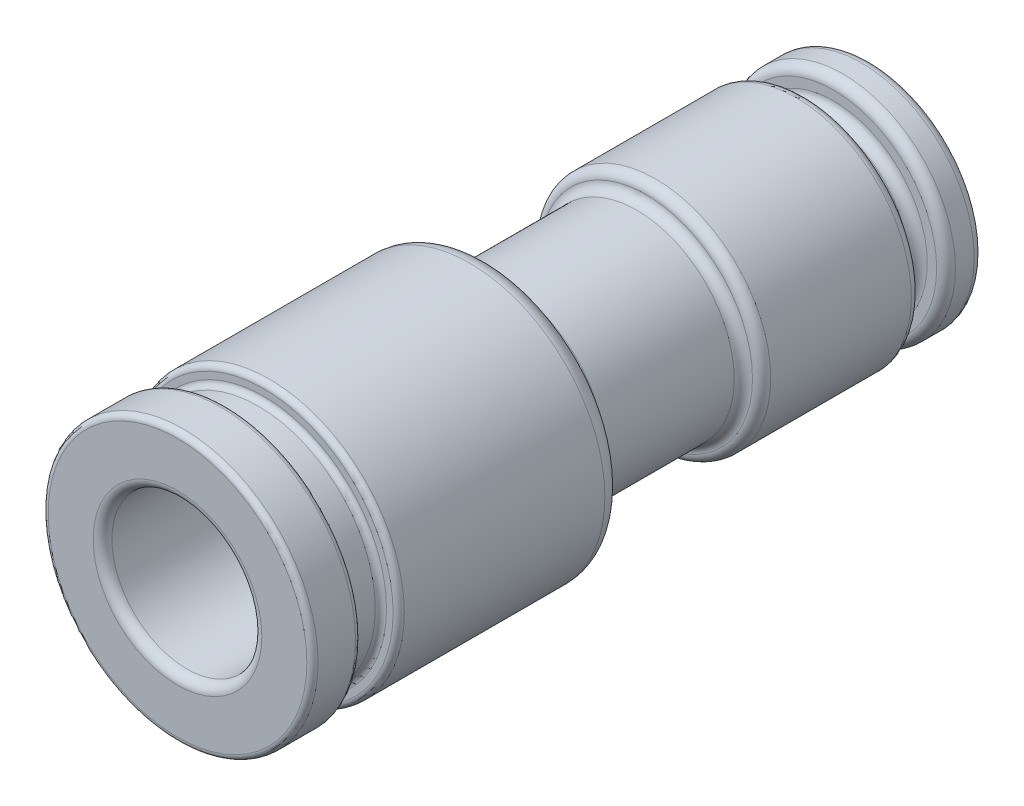
SolidWorks part; units mm, degrees
ref_plane "Front Plane" through (0, 0, 0) normal (0, 0, 1) x (1, 0, 0)
ref_plane "Top Plane" through (0, 0, 0) normal (0, 1, 0) x (1, 0, 0)
ref_plane "Right Plane" through (0, 0, 0) normal (1, 0, 0) x (0, 0, -1)
sketch "Sketch1" plane through (0, 0, 0) normal (0, 0, 1) x (1, 0, 0)
  circle A0 centre (0, 0) radius 6
  dimension "D1" = 12
extrude "Boss-Extrude1" add sketch "Sketch1" along normal blind 2
sketch "Sketch2" plane through (0, 0, 2) normal (0, 0, 1) x (1, 0, 0)
  circle A0 centre (0, 0) radius 4.5
  dimension "D1" = 9
extrude "Boss-Extrude2" add sketch "Sketch2" along normal blind 1.5
sketch "Sketch3" plane through (0, 0, 3.5) normal (0, 0, 1) x (1, 0, 0)
  circle A0 centre (0, 0) radius 6.15
  dimension "D1" = 12.3
extrude "Boss-Extrude3" add sketch "Sketch3" along normal blind 8.5
ref_plane "Plane1" through (0, 0, 12.6) normal (0, 0, 1) x (1, 0, 0)
sketch "Sketch4" plane through (0, 0, 12) normal (0, 0, 1) x (1, 0, 0)
  circle A0 centre (0, 0) radius 5.2
  dimension "D1" = 10.4
extrude "Boss-Extrude6" add sketch "Sketch4" along normal blind 8.4
fillet "Fillet4" radius 0.5 1 edges at (5.2, 0, 12)
fillet "Fillet5" radius 0.5 1 edges at (6.15, 0, 12)
sketch "Sketch7" plane through (0, 0, 20.4) normal (0, 0, 1) x (1, 0, 0)
  circle A0 centre (0, 0) radius 7.2
  dimension "D1" = 14.4
extrude "Boss-Extrude7" add sketch "Sketch7" along normal blind 12
fillet "Fillet6" radius 1 1 edges at (5.2, 0, 20.4)
fillet "Fillet7" radius 1 1 edges at (7.2, 0, 20.4)
sketch "Sketch8" plane through (0, 0, 32.4) normal (0, 0, 1) x (1, 0, 0)
  circle A0 centre (0, 0) radius 6.25
  dimension "D1" = 12.5
extrude "Boss-Extrude8" add sketch "Sketch8" along normal blind 2
sketch "Sketch9" plane through (0, 0, 34.4) normal (0, 0, 1) x (1, 0, 0)
  circle A0 centre (0, 0) radius 7.2
extrude "Boss-Extrude9" add sketch "Sketch9" along normal offset from surface (2.6 mm away) 37 up to face at (6, 0, 0)
fillet "Fillet8" radius 0.3 2 edges at (6.25, 0, 32.4) (6.25, 0, 34.4)
fillet "Fillet9" radius 0.3 3 edges at (7.2, 0, 32.4) (7.2, 0, 37) (7.2, 0, 34.4)
fillet "Fillet10" radius 0.5 5 edges at (6.15, 0, 3.5) (6, 0, 0) (6, 0, 2) (4.5, 0, 2) (4.5, 0, 3.5)
sketch "Sketch10" plane through (0, 0, 37) normal (0, 0, 1) x (1, 0, 0)
  circle A0 centre (0, 0) radius 4
  dimension "D1" = 8
extrude "Cut-Extrude1" cut sketch "Sketch10" against normal blind 15
sketch "Sketch11" plane through (0, 0, 22) normal (0, 0, 1) x (1, 0, 0)
  circle A0 centre (0, 0) radius 3
  dimension "D1" = 6
extrude "Cut-Extrude2" cut sketch "Sketch11" against normal through all
fillet "Fillet11" radius 1 1 edges at (3, 0, 22)
fillet "Fillet12" radius 1 1 edges at (4, 0, 22)
fillet "Fillet13" radius 0.5 1 edges at (4, 0, 37)
fillet "Fillet14" radius 0.5 1 edges at (3, 0, 0)
